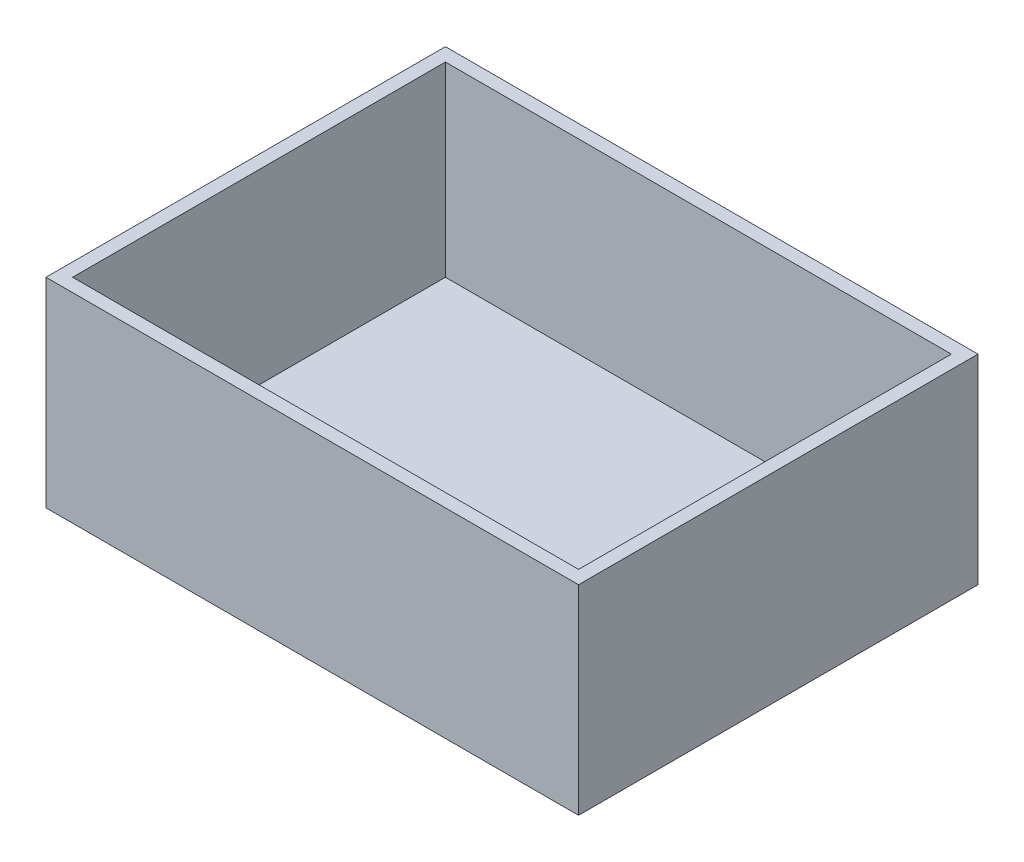
SolidWorks part; units mm, degrees
ref_plane "Alzado" through (0, 0, 0) normal (0, 0, 1) x (1, 0, 0)
ref_plane "Planta" through (0, 0, 0) normal (0, 1, 0) x (1, 0, 0)
ref_plane "Vista lateral" through (0, 0, 0) normal (1, 0, 0) x (0, 0, -1)
sketch "Croquis1" plane through (0, 0, 0) normal (0, 1, 0) x (1, 0, 0)
  line L1 (40, -30) -> (-40, -30)
  line L2 (40, -30) -> (40, 30)
  line L3 (40, 30) -> (-40, 30)
  line L4 (-40, -30) -> (-40, 30)
  line L5 (40, -30) -> (-40, 30) construction
  line L6 (40, 30) -> (-40, -30) construction
  point P0 (0, 0)
  dimension "D1" = 80
  dimension "D2" = 60
extrude "Saliente-Extruir1" add sketch "Croquis1" along normal blind 30
shell "Vaciado1" thickness 2 removed face at (0, 30, 0)
